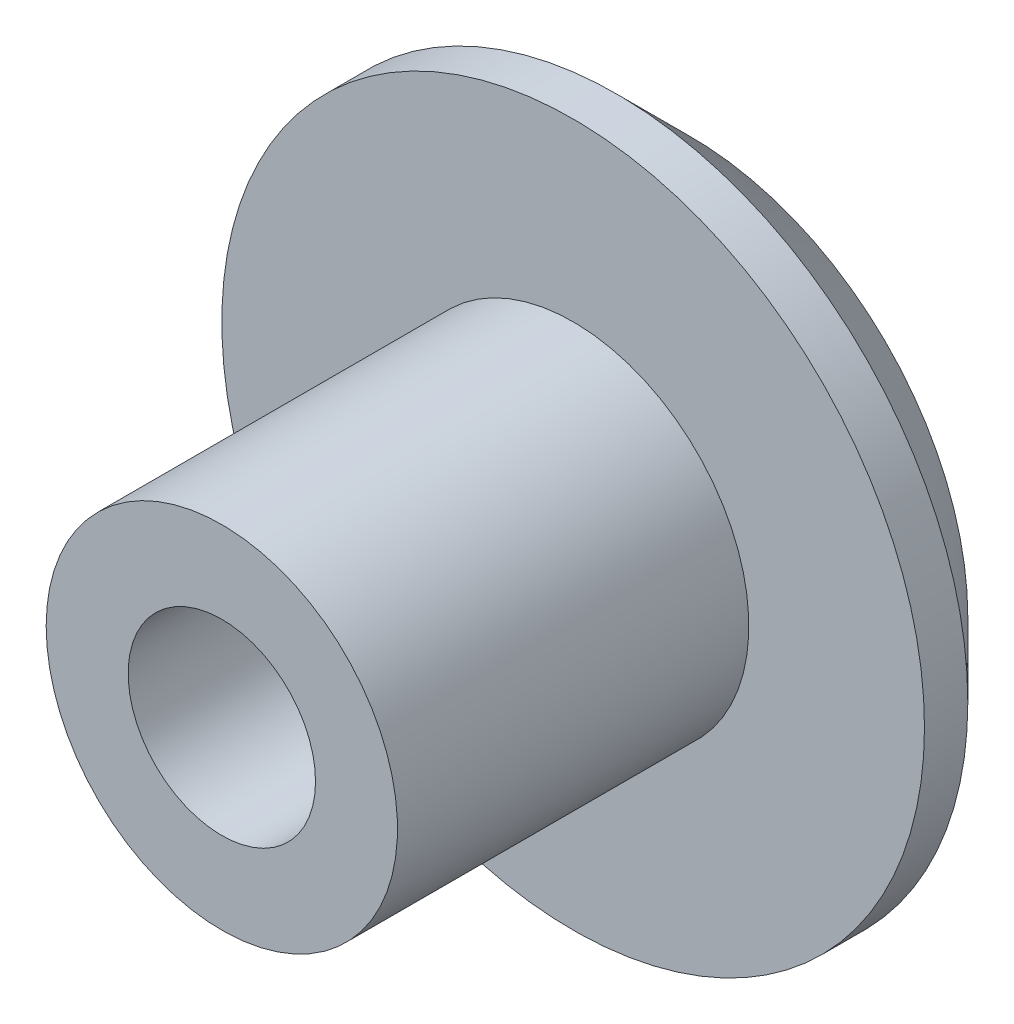
SolidWorks part; units mm, degrees
material "ABS"
ref_plane "Front Plane" through (0, 0, 0) normal (0, 0, 1) x (1, 0, 0)
ref_plane "Top Plane" through (0, 0, 0) normal (0, 1, 0) x (1, 0, 0)
ref_plane "Right Plane" through (0, 0, 0) normal (1, 0, 0) x (0, 0, -1)
sketch "Sketch1" plane through (0, 0, 0) normal (0, 0, 1) x (1, 0, 0)
  circle A0 centre (0, 0) radius 4.7625
extrude "Boss-Extrude1" add sketch "Sketch1" along normal blind 1.5875
sketch "Sketch3" plane through (0, 0, 1.5875) normal (0, 0, 1) x (1, 0, 0)
  circle A0 centre (0, 0) radius 2.3813
extrude "Boss-Extrude2" add sketch "Sketch3" along normal blind 4.7625
sketch "Sketch4" plane through (0, 0, 6.35) normal (0, 0, 1) x (1, 0, 0)
  circle A0 centre (0, 0) radius 1.27
extrude "Cut-Extrude1" cut sketch "Sketch4" against normal through all
chamfer "Chamfer2" distance 1 angle 45 1 edges at (4.7625, 0, 0)
